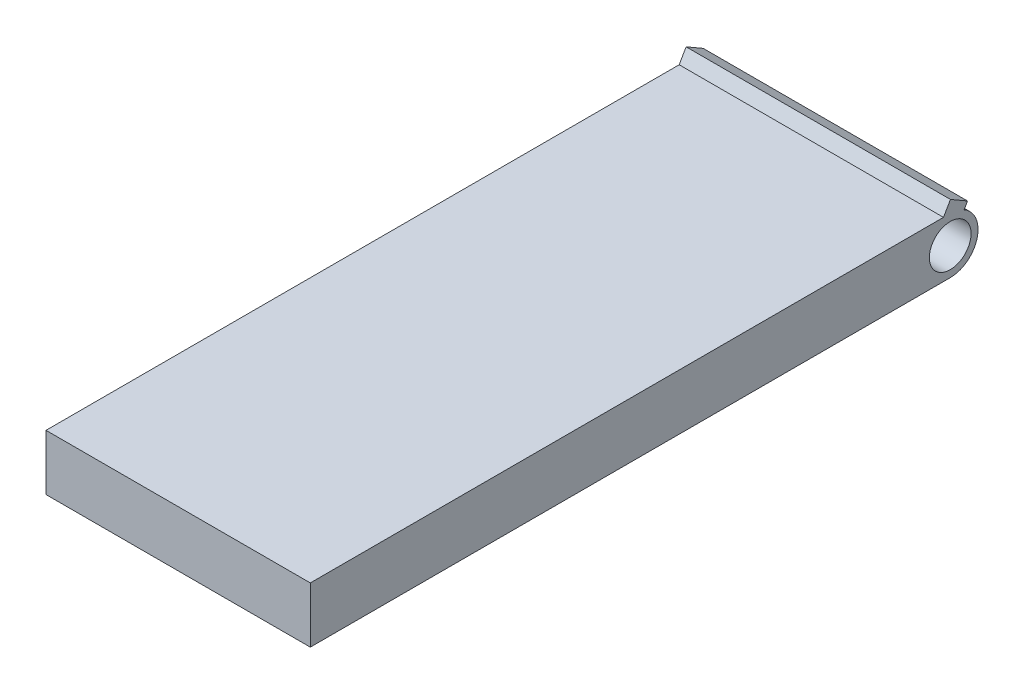
SolidWorks part; units mm, degrees
ref_plane "前视" through (0, 0, 0) normal (0, 0, 1) x (1, 0, 0)
ref_plane "上视" through (0, 0, 0) normal (0, 1, 0) x (1, 0, 0)
ref_plane "右视" through (0, 0, 0) normal (1, 0, 0) x (0, 0, -1)
sketch "草图1" plane through (0, 0, 0) normal (0, 1, 0) x (1, 0, 0)
  line L0 (0, 16.2544) -> (0, -15.5477) construction
  line L1 (-4.75, 12.2619) -> (4.75, 12.2619)
  line L4 (4.75, 12.2619) -> (4.75, -11.7381)
  line L5 (4.75, -11.7381) -> (-4.75, -11.7381)
  line L6 (-4.75, 12.2619) -> (-4.75, -11.7381)
  point P10 (0, -11.7381)
  point P13 (0, 8.2619)
  dimension "D1" = 24
  dimension "D2" = 9.5
extrude "凸台-拉伸1" add sketch "草图1" along normal blind 2
sketch "草图5" plane through (4.75, 0, 0) normal (1, 0, 0) x (0, 0, -1)
  line L0 (12.2619, 1) -> (7.5885, 1) construction
  line L1 (12.2619, 2) -> (12.2619, 0) construction
  line L2 (-11.7381, 2) -> (12.2619, 2) construction
  line L3 (11.2619, 1) -> (12.2619, 2.7321)
  line L4 (11.2619, 2) -> (12.2619, 2)
  line L5 (12.2619, 2) -> (12.2619, 1)
  line L6 (12.2619, 1) -> (12.2619, 0)
  line L7 (12.2619, 0) -> (11.2619, 0)
  line L8 (11.8843, 2.0782) -> (11.2697, 2.433)
  line L9 (11.2697, 2.433) -> (11.0197, 2)
  line L10 (11.2619, 2) -> (11.0197, 2)
  arc A0 (11.2619, 0) -> (11.2619, 2) centre (11.2619, 1) ccw
  circle A1 centre (11.2619, 1) radius 0.75
  point P19 (0, 0)
  point P20 (0, 0)
  line M1 (-11.7381, 0) -> (12.2619, 0)
  line M2 (12.2619, 0) -> (12.2619, 2)
  line M3 (12.2619, 2) -> (-11.7381, 2)
  dimension "D1" = 1.5
  dimension "D3" = 0.25
  dimension "D2" = 1
  dimension "D4" = 60
  dimension "D5" = 0.5
extrude "切除-拉伸4" cut sketch "草图5" against normal through all contours L0 L3 A1 | A1 L0 | L0 A1 L3 | A0 M1 M2 | A0 L3 M2 region at (4.75, 1.7505, -12.0916) region at (4.75, 0.2234, -12.0385) region at (4.75, 0.6817, -11.2619) region at (4.75, 1.2387, -11.6754) region at (4.75, 1.3581, -11.0551)
extrude "凸台-拉伸2" add sketch "草图5<4>" against normal up to surface (9.5 mm away) contours L8 L9 M3 region at (4.75, 2.1483, -11.4203) up to face at (-4.75, 1, -12.0119)
sketch "草图5<4>" plane through (4.75, 0, 0) normal (1, 0, 0) x (0, 0, -1) same geometry as "草图5"
